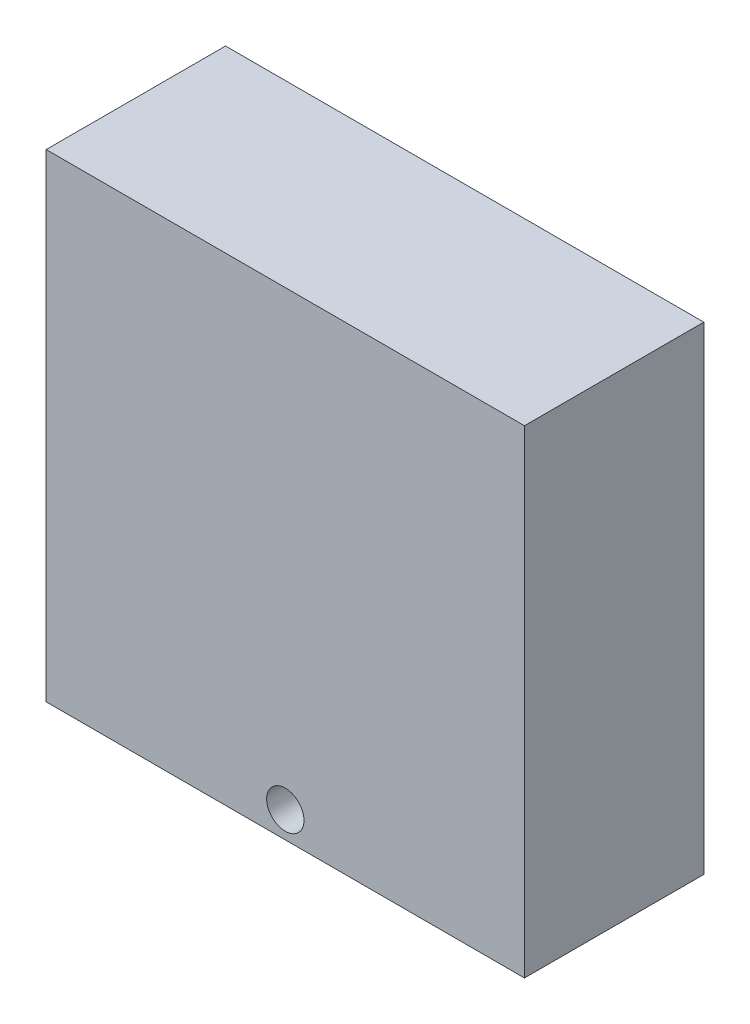
SolidWorks part; units mm, degrees
ref_plane "Plan de face" through (0, 0, 0) normal (0, 0, 1) x (1, 0, 0)
ref_plane "Plan de dessus" through (0, 0, 0) normal (0, 1, 0) x (1, 0, 0)
ref_plane "Plan de droite" through (0, 0, 0) normal (1, 0, 0) x (0, 0, -1)
sketch "Esquisse1" plane through (0, 0, 0) normal (0, 0, 1) x (1, 0, 0)
  line L1 (0, 0) -> (32, 0)
  line L2 (0, 0) -> (0, 32)
  line L3 (0, 32) -> (32, 32)
  line L4 (32, 0) -> (32, 32)
  dimension "D1" = 32
  dimension "D2" = 32
extrude "Boss.-Extru.1" add sketch "Esquisse1" along normal blind 12
sketch "Esquisse2" plane through (0, 0, 0) normal (0, -1, 0) x (1, 0, 0)
  line L0 (4, 0) -> (4, 5)
  line L1 (0, 0) -> (32, 0) construction
  line L2 (4, 5) -> (5, 5)
  line L3 (5, 5) -> (5, 6)
  line L4 (5, 6) -> (4, 6)
  line L5 (4, 6) -> (4, 8)
  line L6 (4, 8) -> (28, 8)
  line L7 (28, 8) -> (28, 6)
  line L8 (28, 6) -> (27, 6)
  line L9 (27, 6) -> (27, 5)
  line L10 (27, 5) -> (28, 5)
  line L11 (28, 5) -> (28, 0)
  line L12 (28, 0) -> (4, 0)
  line L13 (0, 12) -> (32, 12) construction
  point P15 (16, 8)
  point P18 (16, 12)
  dimension "D1" = 24
  dimension "D2" = 1
  dimension "D3" = 1
  dimension "D4" = 5
  dimension "D5" = 8
extrude "Enlèv. mat.-Extru.1" cut sketch "Esquisse2" against normal blind 28
sketch "Esquisse3" plane through (0, 0, 12) normal (0, 0, 1) x (1, 0, 0)
  line L0 (0, 0) -> (32, 0) construction
  circle A0 centre (16, 1.75) radius 1.25
  point P2 (16, 0)
  dimension "D1" = 2.5
  dimension "D2" = 1.75
extrude "Enlèv. mat.-Extru.2" cut sketch "Esquisse3" against normal through all
sketch "Esquisse4" plane through (0, 0, 8) normal (0, 0, -1) x (-1, 0, 0)
  line L3 (-28, 28) -> (-28, 0) construction
  line L4 (-4, 28) -> (-4, 0) construction
  line L5 (-28, 15) -> (-28, 28)
  line L6 (-28, 28) -> (-4, 28)
  line L7 (-4, 28) -> (-4, 15)
  line L8 (-4, 28) -> (-28, 28) construction
  arc A0 (-28, 15) -> (-4, 15) centre (-16, 15) cw
  point P3 (-28, 13.7534)
  dimension "D1" = 12
  dimension "D2" = 13
extrude "Boss.-Extru.2" add sketch "Esquisse4" along normal up to surface (8 mm away) up to face at (16, 15, 0)
sketch "Esquisse5" plane through (0, 0, 5) normal (0, 0, -1) x (-1, 0, 0)
  line L0 (-5, 15) -> (0, 15)
  line L1 (0, 15) -> (0, 32)
  line L2 (0, 32) -> (-32, 32)
  line L3 (-32, 32) -> (-32, 15)
  line L4 (-32, 15) -> (-27, 15)
  line L5 (-32, 0) -> (-32, 32) construction
  line L6 (0, 32) -> (0, 0) construction
  line L7 (-32, 32) -> (0, 32) construction
  line L8 (-27, 19.7958) -> (-27, 0) construction
  arc A0 (-27, 15) -> (-5, 15) centre (-16, 15) cw
  arc A3 (-4, 15) -> (-28, 15) centre (-16, 15) ccw construction
  point P16 (0, 0)
  point P17 (0, 0)
  dimension "D1" = 11
extrude "Boss.-Extru.3" add sketch "Esquisse5" against normal up to surface (1 mm away) up to face at (27.5618, 8.7119, 6)
